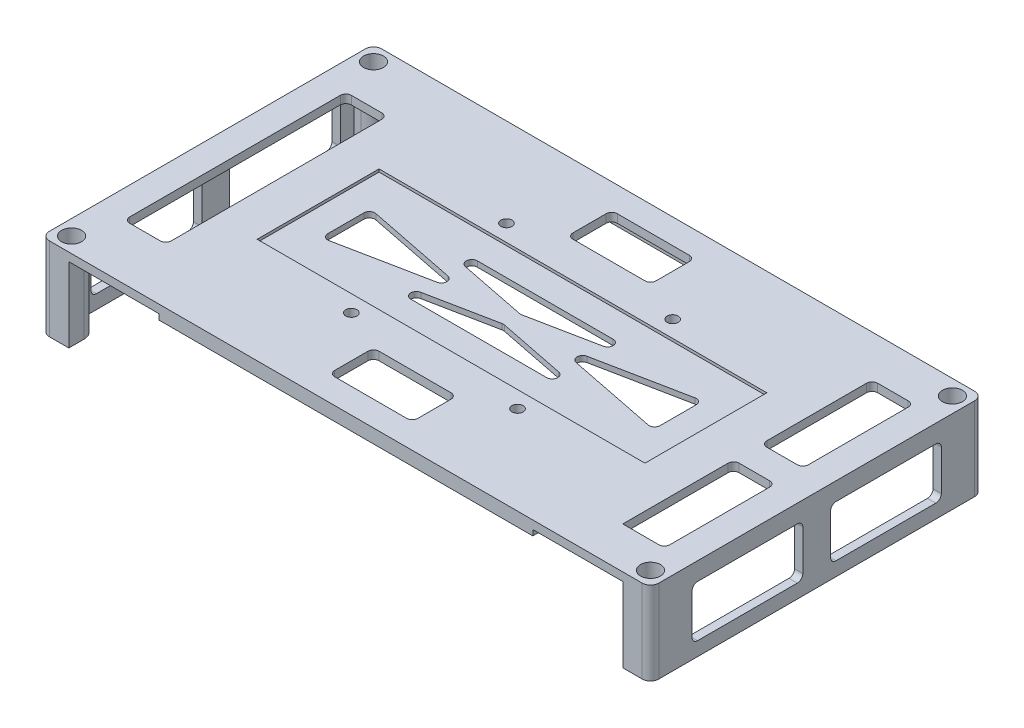
SolidWorks part; units mm, degrees
material "ABS"
ref_plane "前基準面" through (0, 0, 0) normal (0, 0, 1) x (1, 0, 0)
ref_plane "上基準面" through (0, 0, 0) normal (0, 1, 0) x (1, 0, 0)
ref_plane "右基準面" through (0, 0, 0) normal (1, 0, 0) x (0, 0, -1)
sketch "草圖8" plane through (0, 0, 0) normal (0, 1, 0) x (1, 0, 0)
  line L1 (-110, 60) -> (110, 60)
  line L2 (-110, 60) -> (-110, -60)
  line L3 (-110, -60) -> (110, -60)
  line L4 (110, 60) -> (110, -60)
extrude "填料-伸長6" add sketch "草圖8" along normal blind 3
sketch "草圖10" plane through (0, 0, 0) normal (0, -1, 0) x (1, 0, 0)
  line L1 (-110, 60) -> (-100, 60)
  line L2 (-110, 60) -> (-110, -60)
  line L3 (-110, -60) -> (-100, -60)
  line L4 (-100, 60) -> (-100, -60)
  line L5 (0, 0) -> (0, 67.9588) construction
  line L6 (0, 0) -> (59.8785, 0) construction
  line L7 (110, -60) -> (100, -60)
  line L8 (100, 60) -> (100, -60)
  line L9 (110, 60) -> (100, 60)
  line L10 (110, 60) -> (110, -60)
  dimension "D2" = 10
extrude "填料-伸長7" add sketch "草圖10" along normal blind 27
sketch "草圖9" plane through (0, 0, 0) normal (0, 1, 0) x (1, 0, 0)
  line L0 (-1000, 0) -> (49000, 0) construction
  line L1 (0, -994.7968) -> (0, 49005.2032) construction
  line L2 (110, 60) -> (-110, 60) construction
  line L4 (110, -60) -> (110, 60) construction
  circle A0 centre (104.5, 54.5) radius 2.05
  circle A1 centre (-104.5, 54.5) radius 2.05
  circle A2 centre (-104.5, -54.5) radius 2.05
  circle A3 centre (104.5, -54.5) radius 2.05
  circle A6 centre (30, 28) radius 2
  circle A7 centre (-30, 28) radius 2
  circle A8 centre (30, -28) radius 2
  circle A9 centre (-30, -28) radius 2
  dimension "D1" = 4.1
  dimension "D5" = 4
  dimension "D2" = 5.5
  dimension "D3" = 5.5
  dimension "D6" = 30
  dimension "D7" = 28
extrude "除料-伸長1" cut sketch "草圖9" against normal through all and the other way through all contours A1 | A2 | A0 | A3
sketch "草圖11" plane through (0, 3, 0) normal (0, 1, 0) x (1, 0, 0)
  line L0 (0.0013, 21.2615) -> (0.0013, 0) construction
  line L1 (0.0013, 0) -> (-26.9987, 0) construction
  line L2 (110, -60) -> (110, 60) construction
  line L3 (110, 60) -> (-110, 60) construction
  circle A0 centre (-104.4974, 54.5) radius 3.6
  circle A1 centre (-104.4974, -54.5) radius 3.6
  circle A2 centre (104.5, -54.5) radius 3.6
  circle A3 centre (104.5, 54.5) radius 3.6
  dimension "D1" = 7.2
  dimension "D2" = 5.5
  dimension "D4" = 5.5
extrude "除料-伸長2" cut sketch "草圖11" against normal blind 22 contours A1 | A0 | A3 | A2
sketch "草圖13" plane through (0, 0, 0) normal (1, 0, 0) x (0, 0, -1)
  line L0 (0, 0) -> (0, -20.0336) construction
  line L2 (-45, -3.5) -> (-5, -3.5)
  line L3 (-45, -3.5) -> (-45, -22)
  line L4 (-45, -22) -> (-5, -22)
  line L5 (-5, -3.5) -> (-5, -22)
  line L6 (60, -27) -> (-60, -27) construction
  line L8 (45, -3.5) -> (45, -22)
  line L9 (5, -3.5) -> (5, -22)
  line L10 (45, -22) -> (5, -22)
  line L11 (45, -3.5) -> (5, -3.5)
  line L12 (-60, 3) -> (-60, -27) construction
  dimension "D1" = 18.5
  dimension "D2" = 5
  dimension "D3" = 15
  dimension "D4" = 10
extrude "除料-伸長4" cut sketch "草圖13" against normal through all both and the other way through all
sketch "草圖14" plane through (0, 3, 0) normal (0, 1, 0) x (1, 0, 0)
  line L0 (0, 0) -> (-46.215, 0) construction
  line L1 (0, 0) -> (0, 32.6806) construction
  line L3 (-70, -22) -> (70, -22)
  line L4 (-70, -22) -> (-70, 22)
  line L5 (-70, 22) -> (70, 22)
  line L6 (70, -22) -> (70, 22)
  line L7 (-70, -22) -> (70, 22) construction
  line L8 (-70, 22) -> (70, -22) construction
  dimension "D1" = 140
  dimension "D2" = 44
extrude "除料-伸長7" cut sketch "草圖14" against normal blind 1
sketch "草圖15" plane through (0, 3, 0) normal (0, 1, 0) x (1, 0, 0)
  line L0 (0, 0) -> (27.6246, 0) construction
  line L1 (-100, 40) -> (-85, 40)
  line L2 (-100, 40) -> (-100, -40)
  line L3 (-100, -40) -> (-85, -40)
  line L4 (-85, 40) -> (-85, -40)
  line L5 (0, 0) -> (0, 35.214) construction
  line L6 (100, 5) -> (85, 5)
  line L7 (85, 45) -> (85, 5)
  line L8 (100, 45) -> (85, 45)
  line L9 (100, 45) -> (100, 5)
  line L10 (70, 22) -> (-70, 22) construction
  line L11 (-44.7029, -12) -> (44.7029, -12)
  line L12 (-60, -8.9406) -> (-60, 8.9406)
  line L13 (-44.7029, 12) -> (44.7029, 12)
  line L14 (60, -8.9406) -> (60, 8.9406)
  line L15 (-15, -35) -> (15, -35)
  line L16 (0, -3.0594) -> (44.7029, -12)
  line L17 (-70, 22) -> (-70, -22) construction
  line L18 (-60, 8.9406) -> (-15.2971, 0)
  line L19 (-44.7029, -12) -> (0, -3.0594)
  line L20 (-44.7029, 12) -> (0, 3.0594)
  line L21 (-60, -8.9406) -> (-15.2971, 0)
  line L22 (-15, 51) -> (15, 51)
  line L23 (-15, 51) -> (-15, 35)
  line L24 (-15, 35) -> (15, 35)
  line L25 (15, 51) -> (15, 35)
  line L26 (15, -51) -> (15, -35)
  line L27 (-15, -51) -> (15, -51)
  line L28 (15.2971, 0) -> (60, -8.9406)
  line L29 (0, 3.0594) -> (44.7029, 12)
  line L30 (15.2971, 0) -> (60, 8.9406)
  line L31 (-15, -51) -> (-15, -35)
  line L32 (100, -45) -> (100, -5)
  line L33 (100, -45) -> (85, -45)
  line L34 (85, -45) -> (85, -5)
  line L35 (100, -5) -> (85, -5)
  line L36 (110, 60) -> (-110, 60) construction
  dimension "D1" = 40
  dimension "D2" = 85
  dimension "D3" = 15
  dimension "D4" = 10
  dimension "D5" = 10
  dimension "D6" = 30
  dimension "D7" = 16
  dimension "D8" = 35
  dimension "D9" = 85
  dimension "D10" = 80
  dimension "D11" = 15
extrude "除料-伸長8" cut sketch "草圖15" against normal through all
extrude "除料-伸長9" cut sketch "草圖9<5>" along normal through all contours A7 | A6 | A9 | A8
sketch "草圖9<5>" plane through (0, 0, 0) normal (0, 1, 0) x (1, 0, 0) same geometry as "草圖9"
sketch "草圖19" plane through (0, -27, 0) normal (0, -1, 0) x (1, 0, 0)
  line L5 (0, -57.1205) -> (0, 57.1205) construction
  line L6 (0, 0) -> (-76.5655, 0) construction
  line L12 (-100, 54.5) -> (-100, -54.5)
  line L15 (-110, 60) -> (-110, -60) construction
  line L16 (-104.5, 50) -> (-107, 50)
  line L18 (-104.5, -50) -> (-107, -50)
  line L19 (-107, 50) -> (-107, -50)
  line L20 (100, 54.5) -> (100, -54.5)
  line L21 (104.5, -50) -> (107, -50)
  line L22 (107, 50) -> (107, -50)
  line L23 (104.5, 50) -> (107, 50)
  arc A0 (-104.5, 50) -> (-100, 54.5) centre (-104.5, 54.5) ccw
  arc A1 (-104.5, -50) -> (-100, -54.5) centre (-104.5, -54.5) cw
  arc A4 (104.5, 50) -> (100, 54.5) centre (104.5, 54.5) cw
  arc A5 (104.5, -50) -> (100, -54.5) centre (104.5, -54.5) ccw
  point P10 (0, 0)
  dimension "D2" = 9
  dimension "D1" = 3
extrude "除料-伸長13" cut sketch "草圖19" against normal blind 27
sketch "草圖20" plane through (0, 0, 0) normal (0, -1, 0) x (1, 0, 0)
  line L0 (0, 0) -> (0, 103.9697) construction
  line L1 (0, 0) -> (143.2508, 0) construction
  line L2 (-100, 60) -> (100, 60) construction
  line L3 (-67.5, 60) -> (67.5, 60)
  line L4 (-67.5, 60) -> (-67.5, 52)
  line L5 (-67.5, 52) -> (67.5, 52)
  line L6 (67.5, 60) -> (67.5, 52)
  line L7 (-67.5, -52) -> (67.5, -52)
  line L8 (67.5, -60) -> (67.5, -52)
  line L9 (-67.5, -60) -> (67.5, -60)
  line L10 (-67.5, -60) -> (-67.5, -52)
  line L12 (-59, 32.5) -> (-39, 32.5)
  line L13 (-59, 32.5) -> (-59, 25)
  line L14 (-59, 25) -> (-54, 25)
  line L15 (-39, 32.5) -> (-39, 29.5)
  line L28 (-85, 40) -> (-85, -40) construction
  line L31 (-54, 25) -> (-54, 29.5)
  line L32 (-54, 29.5) -> (-39, 29.5)
  line L33 (54, 29.5) -> (39, 29.5)
  line L34 (54, 25) -> (54, 29.5)
  line L35 (39, 32.5) -> (39, 29.5)
  line L36 (59, 25) -> (54, 25)
  line L37 (59, 32.5) -> (59, 25)
  line L38 (59, 32.5) -> (39, 32.5)
  line L39 (59, -32.5) -> (39, -32.5)
  line L40 (59, -32.5) -> (59, -25)
  line L41 (59, -25) -> (54, -25)
  line L42 (39, -32.5) -> (39, -29.5)
  line L43 (54, -25) -> (54, -29.5)
  line L44 (54, -29.5) -> (39, -29.5)
  line L45 (-54, -29.5) -> (-39, -29.5)
  line L46 (-54, -25) -> (-54, -29.5)
  line L47 (-39, -32.5) -> (-39, -29.5)
  line L48 (-59, -25) -> (-54, -25)
  line L49 (-59, -32.5) -> (-59, -25)
  line L50 (-59, -32.5) -> (-39, -32.5)
  dimension "D1" = 135
  dimension "D2" = 8
  dimension "D3" = 20
  dimension "D4" = 7.5
  dimension "D5" = 26
  dimension "D6" = 25
  dimension "D7" = 3
  dimension "D8" = 5
extrude "填料-伸長8" add sketch "草圖20" along normal blind 2
fillet "圓角1" radius 3 4 edges at (-110, -12, 60) (-110, -12, -60) (110, -12, -60) (110, -12, 60)
fillet "圓角2" radius 2 49 edges at (-107, 0, 0) (107, 0, 0) (108.5, -3.5, -5) (108.5, -3.5, 45) (108.5, -22, 45) (108.5, -22, -5) (108.5, -3.5, -45) (108.5, -3.5, 5) (108.5, -22, 5) (108.5, -22, -45) (-108.5, -22, -45) (-108.5, -22, 5) (-108.5, -3.5, -45) (-108.5, -3.5, 5) (-108.5, -22, 45) (-108.5, -3.5, 45) (-108.5, -3.5, -5) (-108.5, -22, -5) (60, 1, -8.9406) (44.7029, 1, -12) (-44.7029, 1, -12) (0, 1, 3.0594) (-44.7029, 1, 12) (44.7029, 1, 12) (-15.2971, 1, 0) (0, 1, -3.0594) (60, 1, 8.9406) (100, 1.5, -5) (15, 1.5, -35) (100, 1.5, 45) (15, 1.5, 51) (-85, 1.5, 40) (-15, 1.5, 51) (85, 1.5, -5) (15.2971, 1, 0) (-100, 1.5, 40) (-15, 1.5, -35) (-60, 1, 8.9406) (-60, 1, -8.9406) (15, 1.5, 35) (-15, 1.5, 35) (85, 1.5, 5) (85, 1.5, -45) (100, 1.5, 5) (100, 1.5, -45) (15, 1.5, -51) (-15, 1.5, -51) (-85, 1.5, -40) (-100, 1.5, -40)
